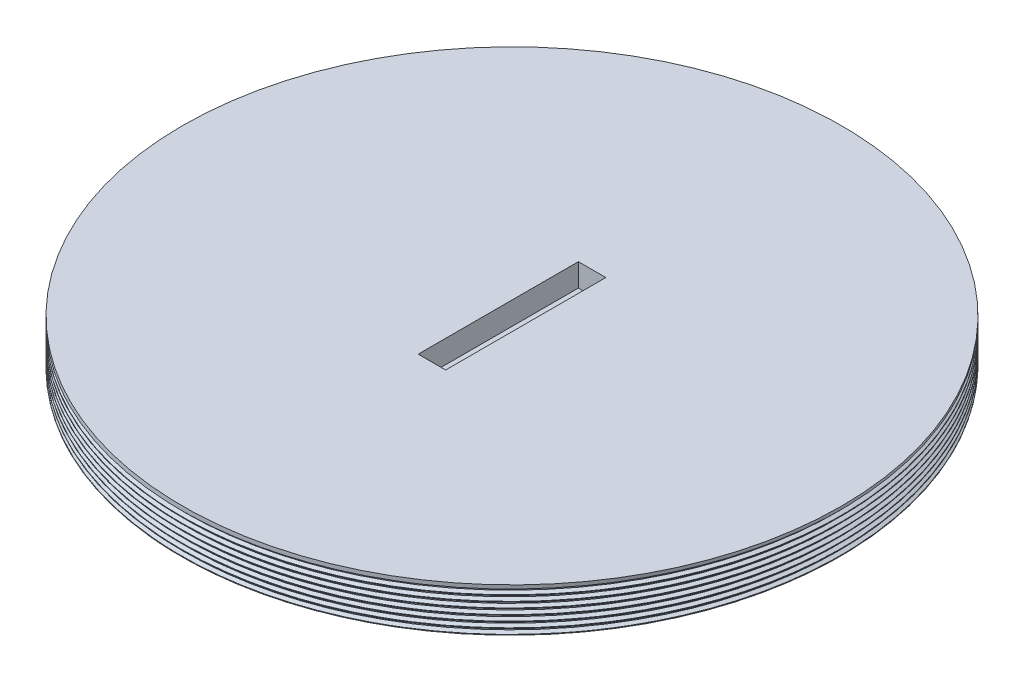
SolidWorks part; units mm, degrees
ref_plane "Front Plane" through (0, 0, 0) normal (0, 0, 1) x (1, 0, 0)
ref_plane "Top Plane" through (0, 0, 0) normal (0, 1, 0) x (1, 0, 0)
ref_plane "Right Plane" through (0, 0, 0) normal (1, 0, 0) x (0, 0, -1)
sketch "Sketch1" plane through (0, 0, 0) normal (0, 1, 0) x (1, 0, 0)
  circle A0 centre (0, 0) radius 14.4
  dimension "D1" = 28.8
extrude "Boss-Extrude1" add sketch "Sketch1" along normal blind 2
thread "Thread1" pitch 0.25 method cut profile "Thread Profile1" start angle 0, offset 0, length 2, pitch 0.25, diameter 28.8
ref_plane "Plane1" through (-14.4, 2, 0) normal (0, 0, 1) x (-1, 0, 0)
sketch "Thread Profile1" plane through (-14.4, 2, 0) normal (0, 0, 1) x (-1, 0, 0)
  line L0 (0, 0) -> (0, 0.25) construction
  line L11 (0, 0) -> (0, 0.2187)
  line L12 (0, 0.2187) -> (-0.1353, 0.1406)
  line L13 (-0.1353, 0.1406) -> (-0.1353, 0.0781)
  line L15 (-0.1353, 0.0781) -> (0, 0)
  line L17 (-0.1353, 0.1094) -> (0, 0.1094) construction
  point P2 (0, 0)
  dimension "Pitch" = 0.25
  dimension "Profile_Angle" = 60
  dimension "Profile_Land" = 0.0625
  dimension "Profile_Height" = 0.1353
sketch "Sketch4" plane through (0, 2, 0) normal (0, 1, 0) x (1, 0, 0)
  line L1 (-0.6, 3.5) -> (0.6, 3.5)
  line L2 (-0.6, 3.5) -> (-0.6, -3.5)
  line L3 (-0.6, -3.5) -> (0.6, -3.5)
  line L4 (0.6, 3.5) -> (0.6, -3.5)
  dimension "D1" = 1.2
  dimension "D2" = 7
  dimension "D3" = 3.5
  dimension "D4" = 0.6
extrude "Cut-Extrude1" cut sketch "Sketch4" against normal blind 1
